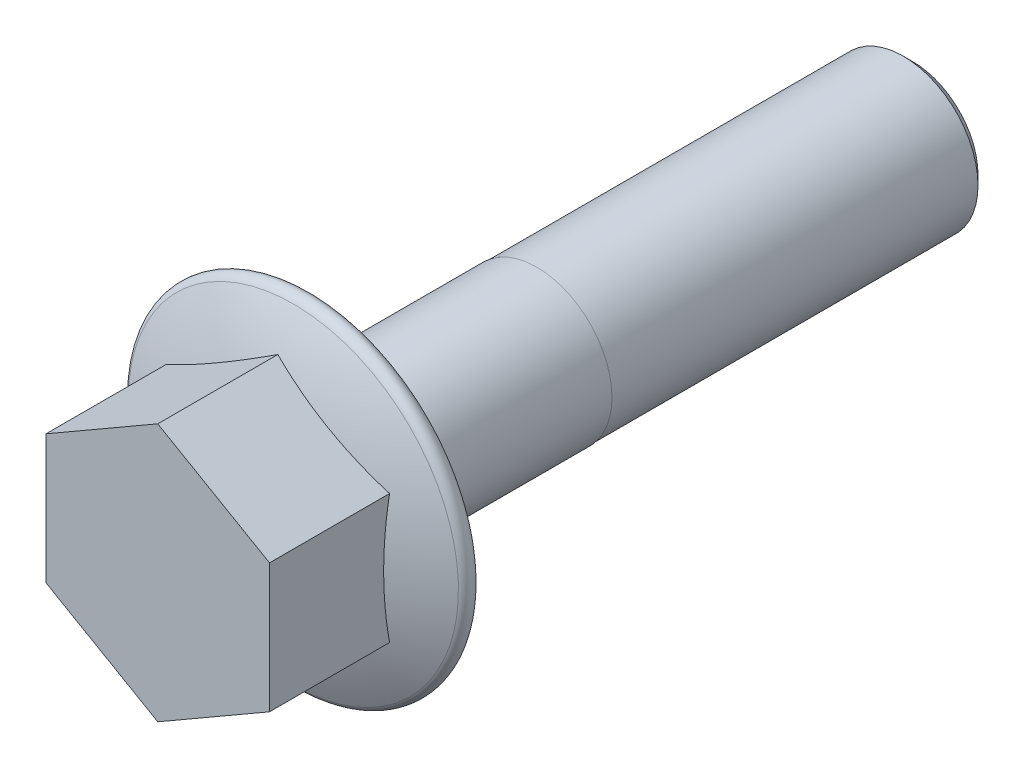
SolidWorks part; units mm, degrees
note: '?' marks a value the reader was unsure of.
ref_plane "Plane1" through (0, 0, 0) normal (0, 0, 1) x (1, 0, 0)
ref_plane "Plane2" through (0, 0, 0) normal (0, 1, 0) x (-1, 0, 0)
ref_plane "Plane3" through (0, 0, 0) normal (1, 0, 0) x (0, 0, -1)
sketch "Head Sketch" plane through (0, 0, 0) normal (0, 0, 1) x (1, 0, 0)
  line L0 (0, 10.8959) -> (9.4361, 5.4479)
  line L1 (9.4361, 5.4479) -> (9.4361, -5.4479)
  line L2 (9.4361, -5.4479) -> (0, -10.8959)
  line L3 (0, -10.8959) -> (-9.4361, -5.4479)
  line L4 (-9.4361, -5.4479) -> (-9.4361, 5.4479)
  line L5 (-9.4361, 5.4479) -> (0, 10.8959)
  line L6 (9.4361, 5.4479) -> (-9.4361, -5.4479) construction
  line L7 (0, 10.8959) -> (0, -10.8959) construction
  line L8 (-9.4361, 5.4479) -> (9.4361, -5.4479) construction
  point P0 (0, 0)
  dimension "D1" = 60
  dimension "D2" = 60
  dimension "Width across flats" = 18.8722
extrude "Head" add sketch "Head Sketch" along normal blind 12.954
sketch "Shank Sketch" plane through (0, 0, 0) normal (0, 0, 1) x (1, 0, 0)
  line L0 (50, 0) -> (-50, 0) construction
  line L1 (0, -50) -> (0, 50) construction
  circle A0 centre (0, 0) radius 6.35
  dimension "Shank diameter" = 12.7
extrude "Shank" add sketch "Shank Sketch" against normal blind 50.8
sketch "Sketch3" plane through (0, 0, 0) normal (0, 1, 0) x (-1, 0, 0)
  line L0 (0, 0) -> (0, 9.525) construction
  line L1 (0, -50.8) -> (0, 0) construction
  line L4 (-13.589, 0) -> (0, 0)
  line L5 (0, 0) -> (0, 4.7625)
  arc A0 (0, 4.7625) -> (-13.9407, 1.5053) centre (0, -26.6992) ccw
  arc A1 (-13.589, 0) -> (-13.9407, 1.5053) centre (-13.589, 0.7937) cw
  dimension "D1" = 0.7937
  dimension "D2" = 27.178
  dimension "D3" = 4.7625
revolve "Flange" add sketch "Sketch3" angle 360 about L0
ref_axis "Axis1" through (0, 0, -105.703) along (0, 0, 1)?
fillet "Fillet2" [suppressed] radius 0.5
sketch "Thread End" plane through (0, 0, 0) normal (1, 0, 0) x (0, 0, -1)
  line L0 (19.05, 6.35) -> (19.05, 6.3)
  line L2 (19.05, 6.3) -> (50.8, 6.3)
  line L3 (50.8, 6.35) -> (19.05, 6.35)
  line L4 (21.5519, 0) -> (27.4271, 0) construction
  line L5 (50.8, 0) -> (0, 0) construction
  line L6 (50.8, -6.35) -> (50.8, 6.35) construction
  line L7 (50.8, 6.3) -> (50.8, 6.35)
  dimension "D1" = 0.05
  dimension "Length of thread" = 31.75
revolve "Thread Cut" cut sketch "Thread End" angle 360 about L4
chamfer "Chamfer1" distance 0.7937 angle 45 1 edges at (6.3, 0, -50.8)
